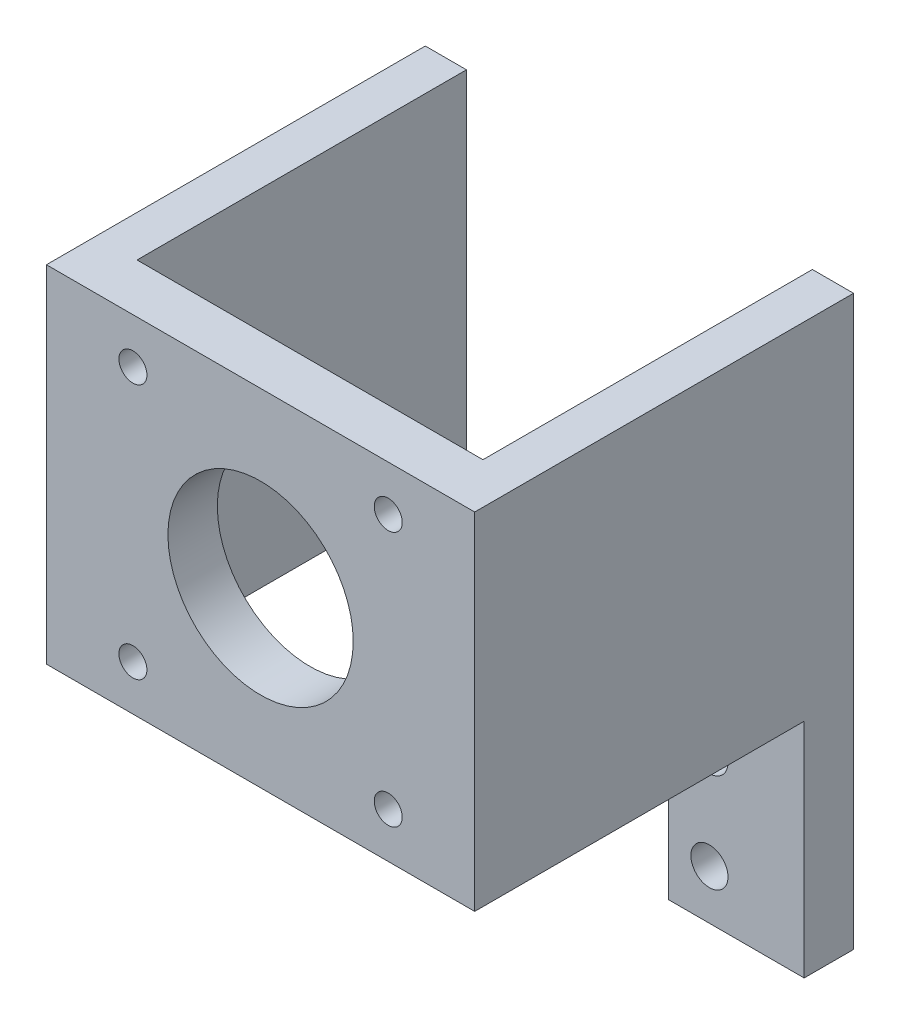
SolidWorks part; units mm, degrees
ref_plane "Спереди" through (0, 0, 0) normal (0, 0, 1) x (1, 0, 0)
ref_plane "Сверху" through (0, 0, 0) normal (0, 1, 0) x (1, 0, 0)
ref_plane "Справа" through (0, 0, 0) normal (1, 0, 0) x (0, 0, -1)
other "Configuration Table"
sketch "Фланец_эскиз" plane through (0, 0, 0) normal (0, 0, 1) x (1, 0, 0)
  line L1 (-26, -21) -> (26, -21)
  line L2 (-26, -21) -> (-26, 21)
  line L3 (-26, 21) -> (26, 21)
  line L4 (26, -21) -> (26, 21)
  line L5 (-26, -21) -> (26, 21) construction
  line L6 (-26, 21) -> (26, -21) construction
  point P0 (0, 0)
  dimension "D1" = 42
  dimension "D2" = 52
extrude "Передняя_пластина" add sketch "Фланец_эскиз" along normal blind 6 from offset 40
sketch "Скоба_эскиз" plane through (0, 0, 0) normal (0, 0, 1) x (1, 0, 0)
  line L0 (-26, -21) -> (-21, -21)
  line L1 (-21, -21) -> (-21, 21)
  line L2 (-21, 21) -> (-26, 21)
  line L3 (-26, 21) -> (-26, -21)
  line L4 (21, -21) -> (26, -21)
  line L5 (26, -21) -> (26, 21)
  line L6 (26, 21) -> (21, 21)
  line L7 (21, 21) -> (21, -21)
  line L8 (-26, -21) -> (26, -21) construction
  point P9 (0, 0)
  point P11 (0, 0)
  point P13 (0, 0)
  point P14 (0, 0)
  point P16 (0, 0)
  point P17 (0, 0)
  point P19 (26.5, 19.0666)
  point P21 (0, 0)
  point P23 (-26, 21)
  point P25 (-26, -21)
  dimension "D1" = 5
extrude "Боковины" add sketch "Скоба_эскиз" along normal blind 40
sketch "Лапки_эскиз" plane through (0, 0, 0) normal (0, 0, 1) x (1, 0, 0)
  line L2 (-26, -21) -> (-9.5, -21)
  line L3 (-26, -21) -> (-26, -48)
  line L4 (-26, -48) -> (-9.5, -48)
  line L5 (-9.5, -48) -> (-9.5, -21)
  line L6 (9.5, -21) -> (26, -21)
  line L11 (26, -21) -> (26, -48)
  line L12 (26, -48) -> (9.5, -48)
  line L13 (9.5, -48) -> (9.5, -21)
  point P0 (26, -21)
  point P1 (26, -21)
  point P2 (-26, -21)
  dimension "D1" = 16.5
  dimension "D4" = 27
extrude "Лапки_основания" add sketch "Лапки_эскиз" along normal blind 6
sketch "Крепёж_фланца_эскиз" plane through (0, 0, 0) normal (0, 0, 1) x (1, 0, 0)
  circle A0 centre (0, 0) radius 11.25
  circle A1 centre (-15.5, -15.5) radius 1.7
  circle A2 centre (-15.5, 15.5) radius 1.7
  circle A3 centre (15.5, -15.5) radius 1.7
  circle A4 centre (15.5, 15.5) radius 1.7
  dimension "D1" = 22.5
  dimension "D4" = 3.4
  dimension "D7" = 3.4
  dimension "D10" = 3.4
  dimension "D13" = 3.4
  dimension "D2" = 15.5
  dimension "D3" = 15.5
  dimension "D5" = 15.5
  dimension "D6" = 15.5
  dimension "D8" = 15.5
  dimension "D9" = 15.5
  dimension "D11" = 15.5
  dimension "D12" = 15.5
extrude "Отверстия_фланца" cut sketch "Крепёж_фланца_эскиз" against normal through all and the other way through all
sketch "Крепёж_основания_эскиз" plane through (0, 0, 0) normal (0, 0, 1) x (1, 0, 0)
  circle A0 centre (-14.5, -30) radius 2.25
  circle A1 centre (-14.5, -42) radius 2.25
  circle A2 centre (14.5, -30) radius 2.25
  circle A3 centre (14.5, -42) radius 2.25
  dimension "D3" = 4.5
  dimension "D6" = 4.5
  dimension "D9" = 4.5
  dimension "D12" = 4.5
  dimension "D1" = 14.5
  dimension "D2" = 30
  dimension "D4" = 14.5
  dimension "D5" = 42
  dimension "D7" = 14.5
  dimension "D8" = 30
  dimension "D10" = 14.5
  dimension "D11" = 42
extrude "Отверстия_основания" cut sketch "Крепёж_основания_эскиз" against normal through all and the other way through all
equation "\"Z корпус\"= 42"
equation "\"Z длина мотора\"= 40"
equation "\"Z зазор\"= 0.5"
equation "\"Z стенка\"= 5"
equation "\"Z пластина\"= 6"
equation "\"Z отступ от края\"= 2"
equation "\"Z лапка\"= 6"
equation "\"Z ширина лапки\"= 10"
equation "\"Z центр лапки\"= 14.5"
equation "\"Z задняя граница\"= 48"
equation "\"Z перекрытие\"= 3"
equation "\"Z шаг М3\"= 31"
equation "\"Z отверстие М3\"= 3.4"
equation "\"Z буртик\"= 22.5"
equation "\"Z отверстие М4\"= 4.5"
equation "\"Z первый ряд М4\"= 30"
equation "\"Z шаг М4\"= 12"
equation "\"D1@Передняя_пластина\" = \"Z пластина\""
equation "\"D19@Передняя_пластина\" = \"Z длина мотора\""
equation "\"D1@Боковины\" = \"Z длина мотора\""
equation "\"D1@Лапки_основания\" = \"Z лапка\""
equation "\"D1@Крепёж_фланца_эскиз\" = \"Z буртик\""
equation "\"D2@Крепёж_фланца_эскиз\" = \"Z шаг М3\"/2"
equation "\"D3@Крепёж_фланца_эскиз\" = \"Z шаг М3\"/2"
equation "\"D4@Крепёж_фланца_эскиз\" = \"Z отверстие М3\""
equation "\"D5@Крепёж_фланца_эскиз\" = \"Z шаг М3\"/2"
equation "\"D6@Крепёж_фланца_эскиз\" = \"Z шаг М3\"/2"
equation "\"D7@Крепёж_фланца_эскиз\" = \"Z отверстие М3\""
equation "\"D8@Крепёж_фланца_эскиз\" = \"Z шаг М3\"/2"
equation "\"D9@Крепёж_фланца_эскиз\" = \"Z шаг М3\"/2"
equation "\"D10@Крепёж_фланца_эскиз\" = \"Z отверстие М3\""
equation "\"D11@Крепёж_фланца_эскиз\" = \"Z шаг М3\"/2"
equation "\"D12@Крепёж_фланца_эскиз\" = \"Z шаг М3\"/2"
equation "\"D13@Крепёж_фланца_эскиз\" = \"Z отверстие М3\""
equation "\"D1@Крепёж_основания_эскиз\" = \"Z центр лапки\""
equation "\"D2@Крепёж_основания_эскиз\" = \"Z первый ряд М4\""
equation "\"D3@Крепёж_основания_эскиз\" = \"Z отверстие М4\""
equation "\"D4@Крепёж_основания_эскиз\" = \"Z центр лапки\""
equation "\"D5@Крепёж_основания_эскиз\" = \"Z первый ряд М4\"+\"Z шаг М4\""
equation "\"D6@Крепёж_основания_эскиз\" = \"Z отверстие М4\""
equation "\"D7@Крепёж_основания_эскиз\" = \"Z центр лапки\""
equation "\"D8@Крепёж_основания_эскиз\" = \"Z первый ряд М4\""
equation "\"D9@Крепёж_основания_эскиз\" = \"Z отверстие М4\""
equation "\"D10@Крепёж_основания_эскиз\" = \"Z центр лапки\""
equation "\"D11@Крепёж_основания_эскиз\" = \"Z первый ряд М4\"+\"Z шаг М4\""
equation "\"D12@Крепёж_основания_эскиз\" = \"Z отверстие М4\""
